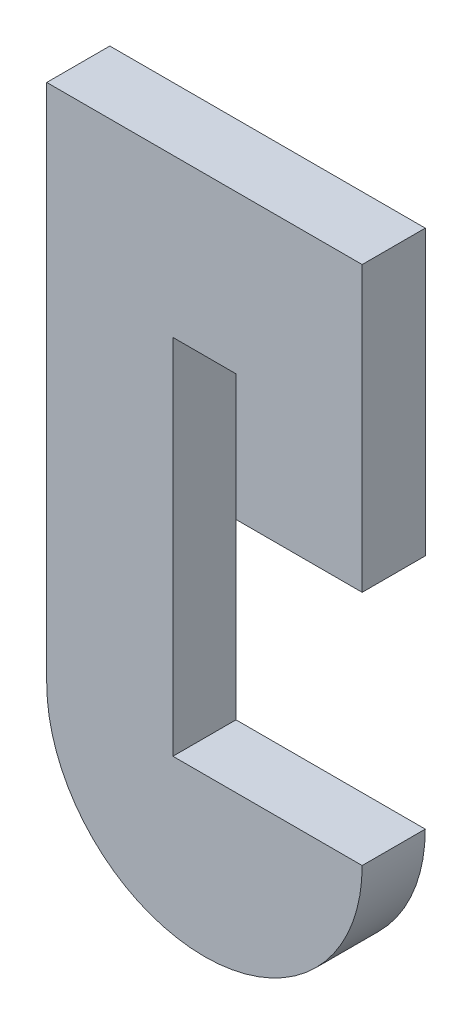
SolidWorks part; units mm, degrees
ref_plane "Front Plane" through (0, 0, 0) normal (0, 0, 1) x (1, 0, 0)
ref_plane "Top Plane" through (0, 0, 0) normal (0, 1, 0) x (1, 0, 0)
ref_plane "Right Plane" through (0, 0, 0) normal (1, 0, 0) x (0, 0, -1)
sketch "Sketch1" plane through (0, 0, 0) normal (0, 0, 1) x (1, 0, 0)
  line L1 (-12.7, -27.305) -> (12.7, -27.305)
  line L2 (-12.7, -27.305) -> (-12.7, 27.305)
  line L3 (-12.7, 27.305) -> (12.7, 27.305)
  line L4 (12.7, -27.305) -> (12.7, 27.305)
  line L5 (-12.7, -27.305) -> (12.7, 27.305) construction
  line L6 (-12.7, 27.305) -> (12.7, -27.305) construction
  point P0 (0, 0)
  dimension "D1" = 25.4
  dimension "D2" = 54.61
extrude "Boss-Extrude1" add sketch "Sketch1" along normal blind 5.08
fillet "Fillet1" radius 12.7 2 edges at (12.7, -27.305, 2.54) (-12.7, -27.305, 2.54)
sketch "Sketch2" plane through (0, 0, 5.08) normal (0, 0, 1) x (1, 0, 0)
  line L1 (12.7, -14.605) -> (-2.54, -14.605)
  line L2 (12.7, -14.605) -> (12.7, 4.445)
  line L3 (12.7, 4.445) -> (-2.54, 4.445)
  line L4 (-2.54, -14.605) -> (-2.54, 4.445)
  dimension "D1" = 15.24
  dimension "D2" = 19.05
extrude "Cut-Extrude1" cut sketch "Sketch2" against normal blind 12.7
sketch "Sketch3" plane through (0, 0, 5.08) normal (0, 0, 1) x (1, 0, 0)
  line L0 (0, 27.305) -> (0, 15.875) construction
  line L1 (12.7, 27.305) -> (-12.7, 27.305) construction
  line L2 (12.7, 4.445) -> (-2.54, 4.445) construction
  line L7 (-2.54, 4.445) -> (2.54, 27.305) construction
  line L8 (-2.2587, 26.039) -> (2.54, 4.445) construction
  line L9 (2.54, 14.605) -> (2.54, 27.305) construction
  line L10 (-2.54, 4.445) -> (2.54, 4.445)
  line L11 (-2.54, 4.445) -> (-2.54, 14.605)
  line L12 (-2.54, 14.605) -> (2.54, 14.605)
  line L13 (2.54, 4.445) -> (2.54, 14.605)
  dimension "D2" = 5.08
extrude "Cut-Extrude2" cut sketch "Sketch3" against normal blind 12.7
equation "\"Foamcore\" = .1in"
equation "\"MDF\" = .2in"
equation "\"Gmaterial\"= \"MDF\""
equation "\"PVC-ID\" = \"1.590in\""
equation "\"PVC-OD\" = \"1.900in\""
equation "\"D1@Boss-Extrude1\"=\"Gmaterial\""
equation "\"D1@Sketch2\"=\"Gmaterial\"/2+.5"
equation "\"D2@Sketch3\"=\"Gmaterial\""
